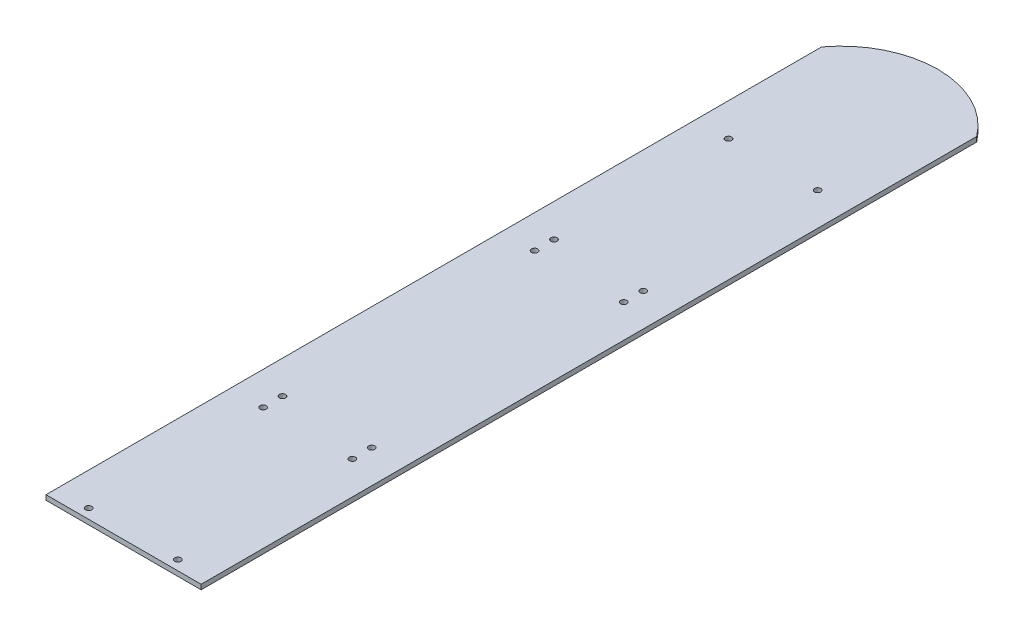
SolidWorks part; units mm, degrees
ref_plane "Front Plane" through (0, 0, 0) normal (0, 0, 1) x (1, 0, 0)
ref_plane "Top Plane" through (0, 0, 0) normal (0, 1, 0) x (1, 0, 0)
ref_plane "Right Plane" through (0, 0, 0) normal (1, 0, 0) x (0, 0, -1)
sketch "Sketch1" plane through (0, 0, 0) normal (0, 1, 0) x (1, 0, 0)
  line L2 (0, 0) -> (0, -508)
  line L3 (0, -508) -> (101.6, -508)
  line L4 (101.6, 0) -> (101.6, -508)
  arc A0 (0, 0) -> (101.6, 0) centre (50.8, -38.1) cw
  dimension "D3" = 63.5
  dimension "D1" = 508
  dimension "D2" = 101.6
extrude "Boss-Extrude1" add sketch "Sketch1" along normal blind 3.175
sketch "Sketch2" plane through (0, 0, 0) normal (0, -1, 0) x (1, 0, 0)
  line L0 (21.59, 82.55) -> (80.01, 82.55) construction
  line L1 (0, 508) -> (101.6, 508) construction
  circle A0 centre (21.59, 501.65) radius 2.032
  circle A1 centre (80.01, 501.65) radius 2.032
  circle A2 centre (21.59, 82.55) radius 2.032
  circle A3 centre (80.01, 82.55) radius 2.032
  arc A4 (0, 0) -> (101.6, 0) centre (50.8, 38.1) ccw construction
  circle A5 centre (21.59, 209.55) radius 2.032
  circle A6 centre (80.01, 209.55) radius 2.032
  circle A7 centre (21.59, 196.85) radius 2.032
  circle A8 centre (80.01, 196.85) radius 2.032
  circle A9 centre (21.59, 374.65) radius 2.032
  circle A10 centre (80.01, 374.65) radius 2.032
  circle A11 centre (21.59, 387.35) radius 2.032
  circle A12 centre (80.01, 387.35) radius 2.032
  point P11 (50.8, -25.4)
  point P12 (50.8, 82.55)
  point P31 (0, 0)
  point P32 (0, 0)
  point P33 (0, 0)
  point P34 (0, 0)
  point P35 (0, 0)
  point P36 (0, 0)
  point P37 (0, 0)
  point P38 (0, 0)
  point P39 (0, 0)
  point P40 (0, 0)
  point P41 (0, 0)
  point P42 (0, 0)
  point P43 (0, 0)
  point P44 (0, 0)
  point P45 (0, 0)
  point P46 (0, 0)
  point P47 (0, 0)
  point P48 (21.59, 344.6262)
  point P49 (21.59, 346.8919)
  point P50 (0, 0)
  point P51 (0, 0)
  point P52 (0, 0)
  point P53 (0, 0)
  point P54 (0, 0)
  point P55 (21.59, 161.4222)
  dimension "D1" = 4.064
  dimension "D2" = 58.42
  dimension "D3" = 6.35
  dimension "D4" = 419.1
  dimension "D5" = 114.3
  dimension "D6" = 177.8
  dimension "D7" = 12.7
  dimension "D8" = 12.7
extrude "Cut-Extrude1" cut sketch "Sketch2" against normal through all
